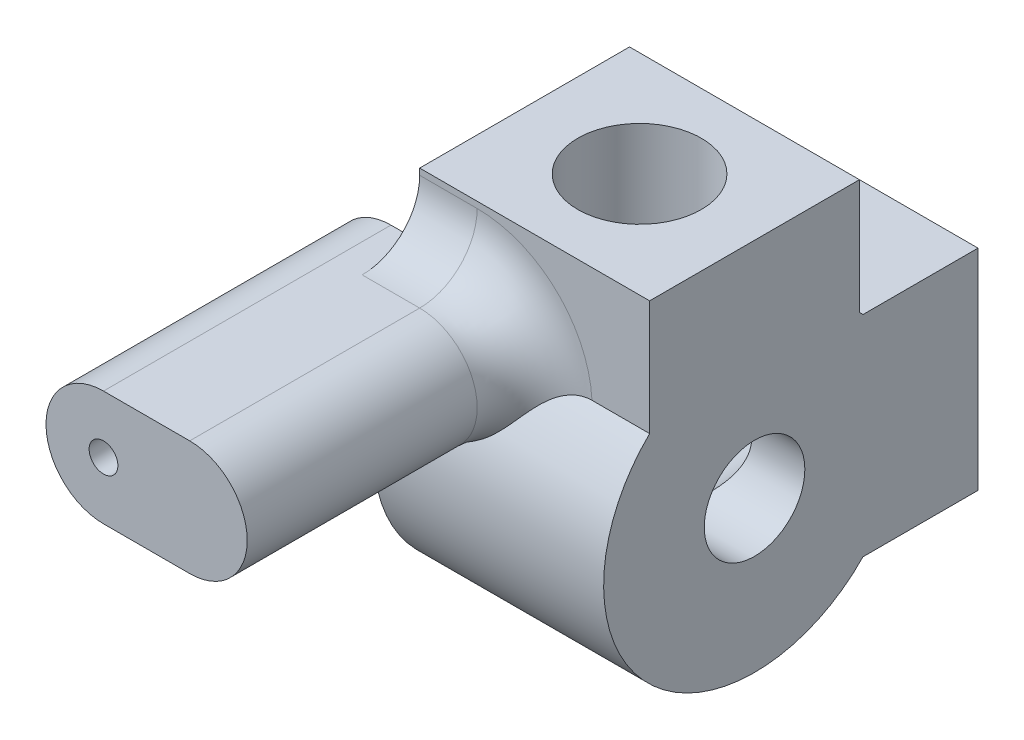
SolidWorks part; units mm, degrees
material "PLA Black"
ref_plane "Front" through (0, 0, 0) normal (0, 0, 1) x (1, 0, 0)
ref_plane "Top" through (0, 0, 0) normal (0, 1, 0) x (1, 0, 0)
ref_plane "Right" through (0, 0, 0) normal (1, 0, 0) x (0, 0, -1)
sketch "Sketch1" plane through (0, 0, 0) normal (1, 0, 0) x (0, 0, -1)
  line L0 (1.118, 1) -> (-1.118, 1) construction
  line L1 (-3.65, 3.7736) -> (3.65, 3.7736)
  line L2 (3.7736, 3.65) -> (3.7736, -3.65)
  line L3 (0, 0) -> (11.6334, 0) construction
  line L4 (0, 0) -> (0, 8.6732) construction
  arc A0 (-1.118, 1) -> (1.118, 1) centre (0, 0) ccw construction
  circle A1 centre (0, 0) radius 1.75
  arc A2 (3.7736, -3.65) -> (-3.65, 3.7736) centre (0, 0) cw
  arc A3 (3.7736, 3.65) -> (3.65, 3.7736) centre (0, 0) ccw
  dimension "D1" = 3
  dimension "D3" = 0.25
  dimension "D5" = 3.5
  dimension "D2" = 1
  dimension "D4" = 7.3
extrude "Boss-Extrude1" add sketch "Sketch1" along normal mid plane 8
sketch "Sketch2" plane through (0, 3.7736, 0) normal (0, 1, 0) x (1, 0, 0)
  circle A0 centre (0, 0) radius 2.15
  dimension "D1" = 4.3
extrude "Cut-Extrude1" cut sketch "Sketch2" against normal blind 5
sketch "Sketch3" plane through (0, 0, -3.7736) normal (0, 0, -1) x (-1, 0, 0)
  circle A0 centre (0, 0) radius 2.15
  dimension "D1" = 4.3
extrude "Cut-Extrude2" cut sketch "Sketch3" against normal blind 5
sketch "Sketch4" plane through (0, 3.7736, 0) normal (0, 1, 0) x (1, 0, 0)
  line L0 (4, 3.65) -> (-4, 3.65) construction
  line L1 (4, 3.65) -> (4, -3.65) construction
  line L2 (4, -3.65) -> (-4, -3.65) construction
  line L3 (-4, 3.65) -> (-4, -3.65) construction
  line L4 (4, 3.65) -> (-4, 3.65)
  line L5 (4, 3.65) -> (4, -3.65)
  line L6 (4, -3.65) -> (-4, -3.65)
  line L7 (-4, 3.65) -> (-4, -3.65)
  circle A0 centre (0, 0) radius 2.15 construction
  circle A1 centre (0, 0) radius 2.15
extrude "Boss-Extrude2" add sketch "Sketch4" along normal blind 4
sketch "Sketch5" plane through (0, 0, -3.7736) normal (0, 0, -1) x (-1, 0, 0)
  line L0 (-4, 3.65) -> (4, 3.65) construction
  line L1 (4, -3.65) -> (4, 3.65) construction
  line L2 (-4, -3.65) -> (4, -3.65) construction
  line L3 (-4, -3.65) -> (-4, 3.65) construction
  line L4 (-4, 3.65) -> (4, 3.65)
  line L5 (4, -3.65) -> (4, 3.65)
  line L6 (-4, -3.65) -> (4, -3.65)
  line L7 (-4, -3.65) -> (-4, 3.65)
  circle A0 centre (0, 0) radius 2.15 construction
  circle A1 centre (0, 0) radius 2.15
extrude "Boss-Extrude3" add sketch "Sketch5" along normal blind 4
ref_axis "Axis1" through (4, 0, 0) along (-1, 0, 0)
sketch "Sketch6" plane through (0, 0, 3.65) normal (0, 0, 1) x (1, 0, 0)
  line L0 (-4, 7.7736) -> (-4, 3.7736) construction
  line L2 (-2, 5.555) -> (-5, 5.555)
  line L3 (-5, 1.555) -> (-2, 1.555)
  line L6 (4, 0) -> (-4, 0) construction
  circle A0 centre (-5, 3.555) radius 0.5
  arc A1 (-5, 5.555) -> (-5, 1.555) centre (-5, 3.555) ccw
  arc A2 (-2, 5.555) -> (-2, 1.555) centre (-2, 3.555) cw
  dimension "D1" = 1
  dimension "D2" = 3.555
  dimension "D3" = 1.5
  dimension "D4" = 1
  dimension "D5" = 3
extrude "Boss-Extrude4" add sketch "Sketch6" along normal blind 10
fillet "Fillet1" radius 2 2 edges at (-0.6653, 5.0445, 3.65) (-3, 5.555, 3.65)
equation "\"knee_angle\"= 70"
equation "\"ankle_angle\" = 90"
equation "\"hip_angle\" = 30"
equation "\"spring_ankle_parallel_arm_diameter\"= 0.89"
equation "\"spring_ankle_parallel_arm_length\"= 13"
equation "\"spring_ankle_parallel_intern_diameter\"= 6.22"
equation "\"spring_ankle_parallel_angle\"= \"ankle_angle\""
equation "\"spring_ankle_parallel_turns\"= 3"
equation "\"spring_ankle_parallel_pitch\"= \"spring_ankle_parallel_arm_diameter\" * 1.01"
equation "\"spring_ankle_parallel_cutting_distance\"= (1-\"spring_ankle_parallel_angle\" / 360) * \"spring_ankle_parallel_pitch\""
equation "\"spring_ankle_serial_arm_diameter\"= 0.89"
equation "\"spring_ankle_serial_arm_length\"= 10"
equation "\"spring_ankle_serial_intern_diameter\"= 6.22"
equation "\"spring_ankle_serial_angle\"= \"90\""
equation "\"spring_ankle_serial_turns\"= 3"
equation "\"spring_ankle_serial_pitch\"= \"spring_ankle_serial_arm_diameter\" * 1.01"
equation "\"spring_ankle_serial_cutting_distance\"= (1-\"spring_ankle_serial_angle\" / 360) * \"spring_ankle_serial_pitch\""
equation "\"spring_knee_parallel_arm_diameter\"= 0.43"
equation "\"spring_knee_parallel_arm_length\"= 15"
equation "\"spring_knee_parallel_intern_diameter\"= 5.46"
equation "\"spring_knee_parallel_angle\"= \"knee_angle\""
equation "\"spring_knee_parallel_turns\"= 3"
equation "\"spring_knee_parallel_pitch\"= \"spring_knee_parallel_arm_diameter\" * 1.01"
equation "\"spring_knee_parallel_cutting_distance\"= (1-\"spring_knee_parallel_angle\" / 360) * \"spring_knee_parallel_pitch\""
equation "\"spring_knee_serial_arm_diameter\"= 0.43"
equation "\"spring_knee_serial_arm_length\"= 10"
equation "\"spring_knee_serial_intern_diameter\"= 5.46"
equation "\"spring_knee_serial_angle\"= \"90\""
equation "\"spring_knee_serial_turns\"= 3"
equation "\"spring_knee_serial_pitch\"= \"spring_knee_serial_arm_diameter\" * 1.01"
equation "\"spring_knee_serial_cutting_distance\"= (1-\"spring_knee_serial_angle\" / 360) * \"spring_knee_serial_pitch\""
equation "\"D2@Sketch6\"=(\"spring_ankle_serial_intern_diameter\" + \"spring_ankle_serial_arm_diameter\")/2"
